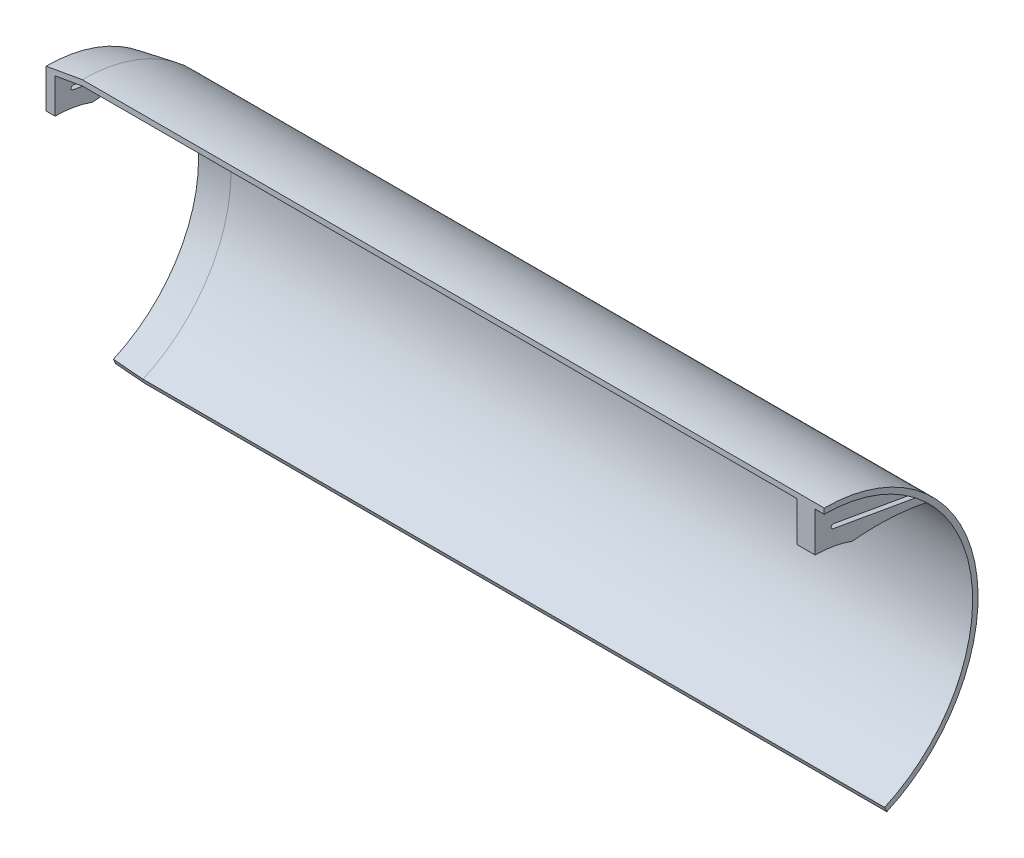
SolidWorks part; units mm, degrees
ref_plane "Front Plane" through (0, 0, 0) normal (0, 0, 1) x (1, 0, 0)
ref_plane "Top Plane" through (0, 0, 0) normal (0, 1, 0) x (1, 0, 0)
ref_plane "Right Plane" through (0, 0, 0) normal (1, 0, 0) x (0, 0, -1)
curve "Curve1"
  spline degree 3 poles (0, 0, 0) (-0.0123, 3.8916, 0) (-0.0274, 8.685, 0) (0.3616, 14.0857, 0) (0.5761, 16.0905, 0) (0.7825, 17.6048, 0) (0.9862, 18.8543, 0) (1.1887, 19.9315, 0) (1.3904, 20.8857, 0) (1.5917, 21.7465, 0) (1.7927, 22.5337, 0) (1.9935, 23.2611, 0) (2.1942, 23.9386, 0) (2.3947, 24.5739, 0) (2.5952, 25.1728, 0) (2.7956, 25.7401, 0) (2.9959, 26.2796, 0) (3.1962, 26.7943, 0) (3.3965, 27.2868, 0) (3.5967, 27.7594, 0) (3.7969, 28.2139, 0) (3.9971, 28.6519, 0) (4.1973, 29.0748, 0) (4.3974, 29.4838, 0) (4.5976, 29.8799, 0) (4.7977, 30.2641, 0) (4.9978, 30.6373, 0) (5.1979, 31.0001, 0) (5.398, 31.3533, 0) (5.5981, 31.6974, 0) (5.7982, 32.033, 0) (5.9983, 32.3606, 0) (6.1984, 32.6807, 0) (6.3985, 32.9935, 0) (6.5985, 33.2996, 0) (6.7986, 33.5993, 0) (6.9986, 33.8929, 0) (7.1987, 34.1806, 0) (7.3987, 34.4628, 0) (7.5988, 34.7397, 0) (7.7988, 35.0115, 0) (7.9989, 35.2785, 0) (8.1989, 35.5408, 0) (8.399, 35.7988, 0) (8.599, 36.0524, 0) (8.799, 36.3019, 0) (8.9991, 36.5476, 0) (9.1991, 36.7894, 0) (9.3991, 37.0275, 0) (9.5992, 37.2622, 0) (9.7992, 37.4934, 0) (9.9992, 37.7214, 0) (10.1992, 37.9461, 0) (10.3993, 38.1679, 0) (10.5993, 38.3866, 0) (10.7993, 38.6025, 0) (10.9993, 38.8156, 0) (11.1993, 39.026, 0) (11.3994, 39.2338, 0) (11.5994, 39.4391, 0) (11.7994, 39.6419, 0) (11.9994, 39.8422, 0) (12.1994, 40.0403, 0) (12.3995, 40.2361, 0) (12.5995, 40.4297, 0) (12.7995, 40.6212, 0) (12.9995, 40.8106, 0) (13.1995, 40.998, 0) (13.3995, 41.1834, 0) (13.5995, 41.3668, 0) (13.7995, 41.5484, 0) (13.9996, 41.7281, 0) (14.1996, 41.9061, 0) (14.3996, 42.0823, 0) (14.5996, 42.2568, 0) (14.7996, 42.4296, 0) (14.9996, 42.6008, 0) (15.1996, 42.7705, 0) (15.3996, 42.9385, 0) (15.5996, 43.1051, 0) (15.7996, 43.2701, 0) (15.9997, 43.4337, 0) (16.1997, 43.5959, 0) (16.3997, 43.7567, 0) (16.5997, 43.9161, 0) (16.7997, 44.0742, 0) (16.9997, 44.2309, 0) (17.1997, 44.3864, 0) (17.3997, 44.5406, 0) (17.5997, 44.6936, 0) (17.7997, 44.8453, 0) (17.9997, 44.9959, 0) (18.1997, 45.1453, 0) (18.3997, 45.2936, 0) (18.5997, 45.4407, 0) (18.7997, 45.5868, 0) (18.9997, 45.7317, 0) (19.1998, 45.8756, 0) (19.3998, 46.0185, 0) (19.5998, 46.1603, 0) (19.7998, 46.3011, 0) (19.9998, 46.4409, 0) (20.1998, 46.5797, 0) (20.3998, 46.7176, 0) (20.5998, 46.8546, 0) (20.7998, 46.9906, 0) (20.9998, 47.1257, 0) (21.1998, 47.2599, 0) (21.3998, 47.3932, 0) (21.5998, 47.5256, 0) (21.7998, 47.6572, 0) (21.9998, 47.788, 0) (22.1998, 47.9179, 0) (22.3998, 48.047, 0) (22.5998, 48.1753, 0) (22.7998, 48.3028, 0) (22.9998, 48.4295, 0) (23.1998, 48.5555, 0) (23.3998, 48.6807, 0) (23.5998, 48.8051, 0) (23.7998, 48.9288, 0) (23.9998, 49.0518, 0) (24.1998, 49.1741, 0) (24.3998, 49.2957, 0) (24.5998, 49.4165, 0) (24.7999, 49.5367, 0) (24.9999, 49.6562, 0) (25.1999, 49.7751, 0) (25.3999, 49.8933, 0) (25.5999, 50.0108, 0) (25.7999, 50.1277, 0) (25.9999, 50.2439, 0) (26.1999, 50.3596, 0) (26.3999, 50.4746, 0) (26.5999, 50.589, 0) (26.7999, 50.7028, 0) (26.9999, 50.8161, 0) (27.1999, 50.9287, 0) (27.3999, 51.0407, 0) (27.5999, 51.1522, 0) (27.7999, 51.2631, 0) (27.9999, 51.3735, 0) (28.1999, 51.4833, 0) (28.3999, 51.5926, 0) (28.5999, 51.7013, 0) (28.7999, 51.8095, 0) (28.9999, 51.9172, 0) (29.1999, 52.0243, 0) (29.3999, 52.131, 0) (29.5999, 52.2371, 0) (29.7999, 52.3428, 0) (29.9999, 52.4479, 0) (30.1999, 52.5526, 0) (30.3999, 52.6567, 0) (30.5999, 52.7604, 0) (30.7999, 52.8636, 0) (30.9999, 52.9664, 0) (31.1999, 53.0687, 0) (31.3999, 53.1705, 0) (31.5999, 53.2719, 0) (31.7999, 53.3728, 0) (31.9999, 53.4733, 0) (32.1999, 53.5733, 0) (32.3999, 53.6729, 0) (32.5999, 53.7721, 0) (32.7999, 53.8709, 0) (32.9999, 53.9692, 0) (33.1999, 54.0671, 0) (33.3999, 54.1646, 0) (33.5999, 54.2617, 0) (33.7999, 54.3584, 0) (33.9999, 54.4547, 0) (34.1999, 54.5506, 0) (34.3999, 54.6461, 0) (34.5999, 54.7412, 0) (34.7999, 54.836, 0) (34.9999, 54.9303, 0) (35.1999, 55.0243, 0) (35.3999, 55.1179, 0) (35.5999, 55.2111, 0) (35.7999, 55.304, 0) (35.9999, 55.3965, 0) (36.1999, 55.4887, 0) (36.3999, 55.5805, 0) (36.5999, 55.6719, 0) (36.7999, 55.763, 0) (36.9999, 55.8537, 0) (37.1999, 55.9441, 0) (37.3999, 56.0342, 0) (37.5999, 56.1239, 0) (37.7999, 56.2133, 0) (37.9999, 56.3024, 0) (38.1999, 56.3911, 0) (38.3999, 56.4795, 0) (38.5999, 56.5676, 0) (38.7999, 56.6554, 0) (38.9999, 56.7428, 0) (39.1999, 56.83, 0) (39.3999, 56.9168, 0) (39.5999, 57.0033, 0) (39.7999, 57.0896, 0) (39.9999, 57.1755, 0) (40.1999, 57.2611, 0) (40.3999, 57.3464, 0) (40.5999, 57.4314, 0) (40.7999, 57.5161, 0) (40.9999, 57.6006, 0) (41.1999, 57.6847, 0) (41.3999, 57.7686, 0) (41.6, 57.8522, 0) (41.8, 57.9355, 0) (42, 58.0185, 0) (42.2, 58.1012, 0) (42.4, 58.1837, 0) (42.6, 58.2659, 0) (42.8, 58.3479, 0) (43, 58.4295, 0) (43.2, 58.5109, 0) (43.4, 58.592, 0) (43.6, 58.6729, 0) (43.8, 58.7535, 0) (44, 58.8339, 0) (44.2, 58.914, 0) (44.4, 58.9938, 0) (44.6, 59.0734, 0) (44.8, 59.1528, 0) (45, 59.2319, 0) (45.2, 59.3107, 0) (45.4, 59.3893, 0) (45.6, 59.4677, 0) (45.8, 59.5458, 0) (46, 59.6237, 0) (46.2, 59.7014, 0) (46.4, 59.7788, 0) (46.6, 59.856, 0) (46.8, 59.9329, 0) (47, 60.0096, 0) (47.2, 60.0861, 0) (47.4, 60.1624, 0) (47.6, 60.2385, 0) (47.8, 60.3143, 0) (48, 60.3899, 0) (48.2, 60.4652, 0) (48.4, 60.5404, 0) (48.6, 60.6153, 0) (48.8, 60.6901, 0) (49, 60.7646, 0) (49.2, 60.8389, 0) (49.4, 60.913, 0) (49.6, 60.9869, 0) (49.8, 61.0605, 0) (50, 61.134, 0) (50.2, 61.2072, 0) (50.4, 61.2803, 0) (50.6, 61.3531, 0) (50.8, 61.4258, 0) (51, 61.4982, 0) (51.2, 61.5705, 0) (51.4, 61.6426, 0) (51.6, 61.7144, 0) (51.8, 61.7861, 0) (52, 61.8575, 0) (52.2, 61.9288, 0) (52.4, 61.9999, 0) (52.6, 62.0708, 0) (52.8, 62.1415, 0) (53, 62.212, 0) (53.2, 62.2824, 0) (53.4, 62.3525, 0) (53.6, 62.4225, 0) (53.8, 62.4923, 0) (54, 62.5619, 0) (54.2, 62.6313, 0) (54.4, 62.7006, 0) (54.6, 62.7696, 0) (54.8, 62.8385, 0) (55, 62.9072, 0) (55.2, 62.9758, 0) (55.4, 63.0441, 0) (55.6, 63.1123, 0) (55.8, 63.1803, 0) (56, 63.2482, 0) (56.2, 63.3159, 0) (56.4, 63.3834, 0) (56.6, 63.4507, 0) (56.8, 63.5179, 0) (57, 63.5849, 0) (57.2, 63.6518, 0) (57.4, 63.7185, 0) (57.6, 63.785, 0) (57.8, 63.8513, 0) (58, 63.9175, 0) (58.2, 63.9836, 0) (58.4, 64.0495, 0) (58.6, 64.1152, 0) (58.8, 64.1808, 0) (59, 64.2462, 0) (59.2, 64.3114, 0) (59.4, 64.3765, 0) (59.6, 64.4415, 0) (59.8, 64.5063, 0) (60, 64.5709, 0) (60.2, 64.6354, 0) (60.4, 64.6998, 0) (60.6, 64.764, 0) (60.8, 64.828, 0) (61, 64.8919, 0) (61.2, 64.9557, 0) (61.4, 65.0193, 0) (61.6, 65.0827, 0) (61.8, 65.1461, 0) (62, 65.2092, 0) (62.2, 65.2723, 0) (62.4, 65.3352, 0) (62.6, 65.3979, 0) (62.8, 65.4605, 0) (63, 65.523, 0) (63.2, 65.5853, 0) (63.4, 65.6475, 0) (63.6, 65.7096, 0) (63.8, 65.7715, 0) (64, 65.8333, 0) (64.2, 65.895, 0) (64.4, 65.9565, 0) (64.6, 66.0179, 0) (64.8, 66.0791, 0) (65, 66.1402, 0) (65.2, 66.2012, 0) (65.4, 66.2621, 0) (65.6, 66.3228, 0) (65.8, 66.3834, 0) (66, 66.4439, 0) (66.2, 66.5042, 0) (66.4, 66.5644, 0) (66.6, 66.6245, 0) (66.8, 66.6845, 0) (67, 66.7443, 0) (67.2, 66.804, 0) (67.4, 66.8636, 0) (67.6, 66.923, 0) (67.8, 66.9824, 0) (68, 67.0416, 0) (68.2, 67.1007, 0) (68.4, 67.1597, 0) (68.6, 67.2185, 0) (68.8, 67.2772, 0) (69, 67.3359, 0) (69.2, 67.3943, 0) (69.4, 67.4527, 0) (69.6, 67.511, 0) (69.8, 67.5691, 0) (70, 67.6271, 0) (70.2, 67.6851, 0) (70.4, 67.7428, 0) (70.6, 67.8005, 0) (70.8, 67.8581, 0) (71, 67.9155, 0) (71.2, 67.9729, 0) (71.4, 68.0301, 0) (71.6, 68.0872, 0) (71.8, 68.1442, 0) (72, 68.2011, 0) (72.2, 68.2579, 0) (72.4, 68.3145, 0) (72.6, 68.3711, 0) (72.8, 68.4276, 0) (73, 68.4839, 0) (73.2, 68.5401, 0) (73.4, 68.5963, 0) (73.6, 68.6523, 0) (73.8, 68.7082, 0) (74, 68.764, 0) (74.2, 68.8197, 0) (74.4, 68.8753, 0) (74.6, 68.9308, 0) (74.8, 68.9862, 0) (75, 69.0415, 0) (75.2, 69.0966, 0) (75.4, 69.1517, 0) (75.6, 69.2067, 0) (75.8, 69.2616, 0) (76, 69.3164, 0) (76.2, 69.371, 0) (76.4, 69.4256, 0) (76.6, 69.4801, 0) (76.8, 69.5344, 0) (77, 69.5887, 0) (77.2, 69.6429, 0) (77.4, 69.697, 0) (77.6, 69.751, 0) (77.8, 69.8048, 0) (78, 69.8586, 0) (78.2, 69.9123, 0) (78.4, 69.9659, 0) (78.6, 70.0194, 0) (78.8, 70.0728, 0) (79, 70.1261, 0) (79.2, 70.1793, 0) (79.4, 70.2324, 0) (79.6, 70.2855, 0) (79.8, 70.3384, 0) (80, 70.3912, 0) (80.2, 70.444, 0) (80.4, 70.4966, 0) (80.6, 70.5492, 0) (80.8, 70.6017, 0) (81, 70.6541, 0) (81.2, 70.7064, 0) (81.4, 70.7586, 0) (81.6, 70.8107, 0) (81.8, 70.8627, 0) (82, 70.9146, 0) (82.2, 70.9665, 0) (82.4, 71.0182, 0) (82.6, 71.0699, 0) (82.8, 71.1215, 0) (83, 71.173, 0) (83.2, 71.2244, 0) (83.4, 71.2757, 0) (83.6, 71.3269, 0) (83.8, 71.3781, 0) (84, 71.4291, 0) (84.2, 71.4801, 0) (84.4, 71.531, 0) (84.6, 71.5818, 0) (84.8, 71.6325, 0) (85, 71.6832, 0) (85.2, 71.7337, 0) (85.4, 71.7842, 0) (85.6, 71.8346, 0) (85.8, 71.8849, 0) (86, 71.9351, 0) (86.2, 71.9853, 0) (86.4, 72.0354, 0) (86.6, 72.0853, 0) (86.8, 72.1352, 0) (87, 72.1851, 0) (87.2, 72.2348, 0) (87.4, 72.2845, 0) (87.6, 72.3341, 0) (87.8, 72.3836, 0) (88, 72.433, 0) (88.2, 72.4823, 0) (88.4, 72.5316, 0) (88.6, 72.5808, 0) (88.8, 72.6299, 0) (89, 72.6789, 0) (89.2, 72.7279, 0) (89.4, 72.7768, 0) (89.6, 72.8256, 0) (89.8, 72.8743, 0) (90, 72.923, 0) (90.2, 72.9716, 0) (90.4, 73.0201, 0) (90.6, 73.0685, 0) (90.8, 73.1168, 0) (91, 73.1651, 0) (91.2, 73.2133, 0) (91.4, 73.2614, 0) (91.6, 73.3095, 0) (91.8, 73.3575, 0) (92, 73.4054, 0) (92.2, 73.4532, 0) (92.4, 73.501, 0) (92.6, 73.5487, 0) (92.8, 73.5963, 0) (93, 73.6439, 0) (93.2, 73.6913, 0) (93.4, 73.7387, 0) (93.6, 73.7861, 0) (93.8, 73.8333, 0) (94, 73.8805, 0) (94.2, 73.9276, 0) (94.4, 73.9747, 0) (94.6, 74.0217, 0) (94.8, 74.0686, 0) (95, 74.1154, 0) (95.2, 74.1622, 0) (95.4, 74.2089, 0) (95.6, 74.2556, 0) (95.8, 74.3021, 0) (96, 74.3486, 0) (96.2, 74.3951, 0) (96.4, 74.4414, 0) (96.6, 74.4877, 0) (96.8, 74.534, 0) (97, 74.5801, 0) (97.2, 74.6262, 0) (97.4, 74.6723, 0) (97.6, 74.7182, 0) (97.8, 74.7641, 0) (98, 74.81, 0) (98.2, 74.8557, 0) (98.4, 74.9014, 0) (98.6, 74.9471, 0) (98.8, 74.9926, 0) (99, 75.0382, 0) (99.2, 75.0836, 0) (99.4, 75.129, 0) (99.6, 75.1743, 0) (99.8, 75.2196, 0) (100, 75.2647, 0) (100.2, 75.3099, 0) (100.4, 75.3549, 0) (100.6, 75.3999, 0) (100.8, 75.4449, 0) (101, 75.4898, 0) (101.2, 75.5346, 0) (101.4, 75.5793, 0) (101.6, 75.624, 0) (101.8, 75.6686, 0) (102, 75.7132, 0) (102.2, 75.7577, 0) (102.4, 75.8022, 0) (102.6, 75.8465, 0) (102.8, 75.8909, 0) (103, 75.9351, 0) (103.2, 75.9793, 0) (103.4, 76.0235, 0) (103.6, 76.0676, 0) (103.8, 76.1116, 0) (104, 76.1556, 0) (104.2, 76.1995, 0) (104.4, 76.2433, 0) (104.6, 76.2871, 0) (104.8, 76.3308, 0) (105, 76.3745, 0) (105.2, 76.4181, 0) (105.4, 76.4617, 0) (105.6, 76.5052, 0) (105.8, 76.5486, 0) (106, 76.592, 0) (106.2, 76.6353, 0) (106.4, 76.6786, 0) (106.6, 76.7218, 0) (106.8, 76.7649, 0) (107, 76.808, 0) (107.2, 76.8511, 0) (107.4, 76.8941, 0) (107.6, 76.937, 0) (107.8, 76.9799, 0) (108, 77.0227, 0) (108.2, 77.0655, 0) (108.4, 77.1082, 0) (108.6, 77.1508, 0) (108.8, 77.1934, 0) (109, 77.236, 0) (109.2, 77.2784, 0) (109.4, 77.3209, 0) (109.6, 77.3633, 0) (109.8, 77.4056, 0) (110, 77.4479, 0) (110.2, 77.4901, 0) (110.4, 77.5322, 0) (110.6, 77.5743, 0) (110.8, 77.6164, 0) (111, 77.6584, 0) (111.2, 77.7004, 0) (111.4, 77.7423, 0) (111.6, 77.7841, 0) (111.8, 77.8259, 0) (112, 77.8676, 0) (112.2, 77.9093, 0) (112.4, 77.951, 0) (112.6, 77.9925, 0) (112.8, 78.0341, 0) (113, 78.0756, 0) (113.2, 78.117, 0) (113.4, 78.1584, 0) (113.6, 78.1997, 0) (113.8, 78.241, 0) (114, 78.2822, 0) (114.2, 78.3234, 0) (114.4, 78.3645, 0) (114.6, 78.4056, 0) (114.8, 78.4466, 0) (115, 78.4876, 0) (115.2, 78.5285, 0) (115.4, 78.5694, 0) (115.6, 78.6102, 0) (115.8, 78.651, 0) (116, 78.6917, 0) (116.2, 78.7324, 0) (116.4, 78.773, 0) (116.6, 78.8136, 0) (116.8, 78.8541, 0) (117, 78.8946, 0) (117.2, 78.935, 0) (117.4, 78.9754, 0) (117.6, 79.0158, 0) (117.8, 79.0561, 0) (118, 79.0963, 0) (118.2, 79.1365, 0) (118.4, 79.1766, 0) (118.6, 79.2167, 0) (118.8, 79.2568, 0) (119, 79.2968, 0) (119.2, 79.3368, 0) (119.4, 79.3767, 0) (119.6, 79.4165, 0) (119.8, 79.4564, 0) (120, 79.4961, 0) (120.2, 79.5358, 0) (120.4, 79.5755, 0) (120.6, 79.6152, 0) (120.8, 79.6547, 0) (121, 79.6943, 0) (121.2, 79.7338, 0) (121.4, 79.7732, 0) (121.6, 79.8126, 0) (121.8, 79.852, 0) (122, 79.8913, 0) (122.2, 79.9306, 0) (122.4, 79.9698, 0) (122.6, 80.009, 0) (122.8, 80.0481, 0) (123, 80.0872, 0) (123.2, 80.1262, 0) (123.4, 80.1652, 0) (123.6, 80.2042, 0) (123.8, 80.2431, 0) (124, 80.282, 0) (124.2, 80.3208, 0) (124.4, 80.3596, 0) (124.6, 80.3983, 0) (124.8, 80.437, 0) (125, 80.4757, 0) (125.2, 80.5143, 0) (125.4, 80.5528, 0) (125.6, 80.5914, 0) (125.8, 80.6298, 0) (126, 80.6683, 0) (126.2, 80.7067, 0) (126.4, 80.745, 0) (126.6, 80.7833, 0) (126.8, 80.8216, 0) (127, 80.8598, 0) (127.2, 80.898, 0) (127.4, 80.9361, 0) (127.6, 80.9742, 0) (127.8, 81.0123, 0) (128, 81.0503, 0) (128.2, 81.0883, 0) (128.4, 81.1262, 0) (128.6, 81.1641, 0) (128.8, 81.2019, 0) (129, 81.2397, 0) (129.2, 81.2775, 0) (129.4, 81.3152, 0) (129.6, 81.3529, 0) (129.8, 81.3906, 0) (130, 81.4282, 0) (130.2, 81.4657, 0) (130.4, 81.5032, 0) (130.6, 81.5407, 0) (130.8, 81.5782, 0) (131, 81.6156, 0) (131.2, 81.6529, 0) (131.4, 81.6902, 0) (131.6, 81.7275, 0) (131.8, 81.7648, 0) (132, 81.802, 0) (132.2, 81.8391, 0) (132.4, 81.8763, 0) (132.6, 81.9133, 0) (132.8, 81.9504, 0) (133, 81.9874, 0) (133.2, 82.0244, 0) (133.4, 82.0613, 0) (133.6, 82.0982, 0) (133.8, 82.135, 0) (134, 82.1718, 0) (134.2, 82.2086, 0) (134.4, 82.2454, 0) (134.6, 82.282, 0) (134.8, 82.3187, 0) (135, 82.3553, 0) (135.2, 82.3919, 0) (135.4, 82.4285, 0) (135.6, 82.465, 0) (135.8, 82.5014, 0) (136, 82.5379, 0) (136.2, 82.5743, 0) (136.4, 82.6106, 0) (136.6, 82.6469, 0) (136.8, 82.6832, 0) (137, 82.7195, 0) (137.2, 82.7557, 0) (137.4, 82.7919, 0) (137.6, 82.828, 0) (137.8, 82.8641, 0) (138, 82.9001, 0) (138.2, 82.9362, 0) (138.4, 82.9722, 0) (138.6, 83.0081, 0) (138.8, 83.044, 0) (139, 83.0799, 0) (139.2, 83.1158, 0) (139.4, 83.1516, 0) (139.6, 83.1873, 0) (139.8, 83.2231, 0) (140, 83.2588, 0) (140.2, 83.2944, 0) (140.4, 83.3301, 0) (140.6, 83.3657, 0) (140.8, 83.4012, 0) (141, 83.4367, 0) (141.2, 83.4722, 0) (141.4, 83.5077, 0) (141.6, 83.5431, 0) (141.8, 83.5785, 0) (142, 83.6138, 0) (142.2, 83.6491, 0) (142.4, 83.6844, 0) (142.6, 83.7197, 0) (142.8, 83.7549, 0) (143, 83.79, 0) (143.2, 83.8252, 0) (143.4, 83.8603, 0) (143.6, 83.8954, 0) (143.8, 83.9304, 0) (144, 83.9654, 0) (144.2, 84.0004, 0) (144.4, 84.0353, 0) (144.6, 84.0702, 0) (144.8, 84.1051, 0) (145, 84.1399, 0) (145.2, 84.1747, 0) (145.4, 84.2095, 0) (145.6, 84.2442, 0) (145.8, 84.2789, 0) (146, 84.3136, 0) (146.2, 84.3482, 0) (146.4, 84.3828, 0) (146.6, 84.4174, 0) (146.8, 84.4519, 0) (147, 84.4864, 0) (147.2, 84.5209, 0) (147.4, 84.5553, 0) (147.6, 84.5897, 0) (147.8, 84.6241, 0) (148, 84.6584, 0) (148.2, 84.6927, 0) (148.4, 84.727, 0) (148.6, 84.7612, 0) (148.8, 84.7954, 0) (149, 84.8296, 0) (149.2, 84.8638, 0) (149.4, 84.8979, 0) (149.6, 84.9319, 0) (149.8, 84.966, 0) (149.9333, 84.9887, 0) (150, 85, 0) knots 0 0 0 0 0.061462 0.075706 0.085548 0.093322 0.099856 0.105554 0.110643 0.115268 0.119525 0.123482 0.127192 0.130691 0.13401 0.137173 0.140199 0.143104 0.145901 0.148602 0.151215 0.15375 0.156213 0.158609 0.160946 0.163227 0.165456 0.167638 0.169775 0.171871 0.173928 0.17595 0.177937 0.179893 0.181819 0.183716 0.185587 0.187433 0.189255 0.191054 0.192831 0.194589 0.196326 0.198045 0.199747 0.201431 0.2031 0.204753 0.206391 0.208015 0.209626 0.211223 0.212808 0.214381 0.215942 0.217493 0.219032 0.220561 0.22208 0.22359 0.225091 0.226582 0.228065 0.229539 0.231006 0.232464 0.233915 0.235359 0.236795 0.238225 0.239648 0.241065 0.242475 0.243879 0.245277 0.24667 0.248057 0.249438 0.250814 0.252185 0.253551 0.254913 0.256269 0.257621 0.258968 0.260311 0.26165 0.262984 0.264315 0.265641 0.266964 0.268282 0.269598 0.270909 0.272217 0.273522 0.274823 0.276121 0.277416 0.278707 0.279996 0.281281 0.282564 0.283843 0.28512 0.286394 0.287666 0.288935 0.290201 0.291465 0.292726 0.293985 0.295241 0.296495 0.297747 0.298996 0.300243 0.301489 0.302732 0.303972 0.305211 0.306448 0.307683 0.308916 0.310147 0.311376 0.312604 0.313829 0.315053 0.316275 0.317495 0.318714 0.319931 0.321147 0.32236 0.323573 0.324783 0.325993 0.3272 0.328406 0.329611 0.330815 0.332017 0.333217 0.334416 0.335614 0.336811 0.338006 0.3392 0.340393 0.341584 0.342775 0.343964 0.345152 0.346339 0.347524 0.348709 0.349892 0.351074 0.352256 0.353436 0.354615 0.355793 0.35697 0.358146 0.359321 0.360495 0.361668 0.36284 0.364011 0.365182 0.366351 0.36752 0.368687 0.369854 0.37102 0.372185 0.373349 0.374512 0.375674 0.376836 0.377997 0.379157 0.380316 0.381475 0.382632 0.383789 0.384946 0.386101 0.387256 0.38841 0.389563 0.390716 0.391868 0.393019 0.39417 0.39532 0.396469 0.397618 0.398766 0.399913 0.40106 0.402206 0.403351 0.404496 0.40564 0.406784 0.407927 0.409069 0.410211 0.411353 0.412493 0.413633 0.414773 0.415912 0.417051 0.418189 0.419326 0.420463 0.4216 0.422736 0.423871 0.425006 0.426141 0.427275 0.428408 0.429541 0.430674 0.431806 0.432937 0.434068 0.435199 0.436329 0.437459 0.438588 0.439717 0.440846 0.441974 0.443101 0.444229 0.445355 0.446482 0.447608 0.448733 0.449858 0.450983 0.452107 0.453231 0.454355 0.455478 0.456601 0.457723 0.458845 0.459967 0.461088 0.462209 0.46333 0.46445 0.46557 0.46669 0.467809 0.468928 0.470046 0.471164 0.472282 0.4734 0.474517 0.475634 0.47675 0.477866 0.478982 0.480098 0.481213 0.482328 0.483443 0.484557 0.485671 0.486785 0.487898 0.489011 0.490124 0.491237 0.492349 0.493461 0.494573 0.495684 0.496796 0.497906 0.499017 0.500127 0.501237 0.502347 0.503457 0.504566 0.505675 0.506784 0.507892 0.509001 0.510109 0.511216 0.512324 0.513431 0.514538 0.515645 0.516752 0.517858 0.518964 0.52007 0.521175 0.522281 0.523386 0.524491 0.525595 0.5267 0.527804 0.528908 0.530012 0.531116 0.532219 0.533322 0.534425 0.535528 0.53663 0.537733 0.538835 0.539937 0.541038 0.54214 0.543241 0.544342 0.545443 0.546544 0.547644 0.548745 0.549845 0.550945 0.552044 0.553144 0.554243 0.555342 0.556441 0.55754 0.558639 0.559737 0.560836 0.561934 0.563032 0.564129 0.565227 0.566324 0.567421 0.568518 0.569615 0.570712 0.571809 0.572905 0.574001 0.575097 0.576193 0.577289 0.578384 0.57948 0.580575 0.58167 0.582765 0.58386 0.584954 0.586049 0.587143 0.588237 0.589331 0.590425 0.591519 0.592612 0.593706 0.594799 0.595892 0.596985 0.598078 0.59917 0.600263 0.601355 0.602448 0.60354 0.604632 0.605724 0.606815 0.607907 0.608998 0.61009 0.611181 0.612272 0.613363 0.614453 0.615544 0.616635 0.617725 0.618815 0.619905 0.620995 0.622085 0.623175 0.624265 0.625354 0.626443 0.627533 0.628622 0.629711 0.6308 0.631888 0.632977 0.634066 0.635154 0.636242 0.637331 0.638419 0.639507 0.640594 0.641682 0.64277 0.643857 0.644945 0.646032 0.647119 0.648206 0.649293 0.65038 0.651467 0.652553 0.65364 0.654726 0.655813 0.656899 0.657985 0.659071 0.660157 0.661243 0.662328 0.663414 0.664499 0.665585 0.66667 0.667755 0.66884 0.669925 0.67101 0.672095 0.67318 0.674264 0.675349 0.676433 0.677518 0.678602 0.679686 0.68077 0.681854 0.682938 0.684022 0.685105 0.686189 0.687272 0.688356 0.689439 0.690522 0.691605 0.692688 0.693771 0.694854 0.695937 0.69702 0.698102 0.699185 0.700267 0.70135 0.702432 0.703514 0.704596 0.705678 0.70676 0.707842 0.708924 0.710006 0.711087 0.712169 0.71325 0.714332 0.715413 0.716494 0.717575 0.718656 0.719737 0.720818 0.721899 0.72298 0.724061 0.725141 0.726222 0.727302 0.728382 0.729463 0.730543 0.731623 0.732703 0.733783 0.734863 0.735943 0.737023 0.738103 0.739182 0.740262 0.741341 0.742421 0.7435 0.744579 0.745659 0.746738 0.747817 0.748896 0.749975 0.751054 0.752133 0.753211 0.75429 0.755369 0.756447 0.757526 0.758604 0.759682 0.760761 0.761839 0.762917 0.763995 0.765073 0.766151 0.767229 0.768307 0.769385 0.770462 0.77154 0.772618 0.773695 0.774773 0.77585 0.776927 0.778005 0.779082 0.780159 0.781236 0.782313 0.78339 0.784467 0.785544 0.786621 0.787698 0.788774 0.789851 0.790928 0.792004 0.793081 0.794157 0.795233 0.79631 0.797386 0.798462 0.799538 0.800614 0.80169 0.802766 0.803842 0.804918 0.805994 0.80707 0.808145 0.809221 0.810296 0.811372 0.812447 0.813523 0.814598 0.815674 0.816749 0.817824 0.818899 0.819974 0.821049 0.822124 0.823199 0.824274 0.825349 0.826424 0.827499 0.828573 0.829648 0.830723 0.831797 0.832872 0.833946 0.835021 0.836095 0.837169 0.838244 0.839318 0.840392 0.841466 0.84254 0.843614 0.844688 0.845762 0.846836 0.84791 0.848984 0.850058 0.851131 0.852205 0.853279 0.854352 0.855426 0.856499 0.857573 0.858646 0.859719 0.860793 0.861866 0.862939 0.864012 0.865085 0.866159 0.867232 0.868305 0.869378 0.87045 0.871523 0.872596 0.873669 0.874742 0.875814 0.876887 0.87796 0.879032 0.880105 0.881177 0.88225 0.883322 0.884395 0.885467 0.886539 0.887611 0.888684 0.889756 0.890828 0.8919 0.892972 0.894044 0.895116 0.896188 0.89726 0.898332 0.899404 0.900475 0.901547 0.902619 0.90369 0.904762 0.905834 0.906905 0.907977 0.909048 0.91012 0.911191 0.912262 0.913334 0.914405 0.915476 0.916548 0.917619 0.91869 0.919761 0.920832 0.921903 0.922974 0.924045 0.925116 0.926187 0.927258 0.928329 0.929399 0.93047 0.931541 0.932612 0.933682 0.934753 0.935823 0.936894 0.937965 0.939035 0.940105 0.941176 0.942246 0.943317 0.944387 0.945457 0.946527 0.947598 0.948668 0.949738 0.950808 0.951878 0.952948 0.954018 0.955088 0.956158 0.957228 0.958298 0.959368 0.960438 0.961508 0.962577 0.963647 0.964717 0.965786 0.966856 0.967926 0.968995 0.970065 0.971134 0.972204 0.973273 0.974343 0.975412 0.976481 0.977551 0.97862 0.979689 0.980759 0.981828 0.982897 0.983966 0.985035 0.986104 0.987173 0.988242 0.989311 0.99038 0.991449 0.992518 0.993587 0.994656 0.995725 0.996794 0.997863 0.998931 1 1 1 1
sketch "Sketch1" plane through (0, 0, 0) normal (0, 0, 1) x (1, 0, 0)
  line L0 (150, 85) -> (560, 85)
  line L1 (150.2533, 82) -> (560, 82)
  line L2 (560, 85) -> (560, 82)
  line L3 (0, 0) -> (3, 0)
  line L4 (3, 0.0095) -> (3, 0)
  line L5 (3, 0) -> (560, 0) construction
  line L6 (560, 0) -> (560, 82) construction
  line L7 (540, 75) -> (135, 75) construction
  line L8 (135, 75) -> (135, 0) construction
  line L9 (130, 78.3755) -> (135, 78.3755)
  line L12 (135, 79.3054) -> (135, 60)
  line L13 (135, 60) -> (130, 60)
  line L14 (130, 60) -> (130, 81.4281)
  line L15 (555, 60) -> (555, 82)
  line L16 (545, 82) -> (545, 60)
  line L17 (545, 60) -> (555, 60)
  spline S0 degree 3 poles (-1988.6566, -159.7184) (98.3599, -158.1291) (-5.7084, -70.1856) (0.3616, 14.0857) (0.5761, 16.0905) (0.7825, 17.6048) (0.9862, 18.8543) (1.1887, 19.9315) (1.3904, 20.8857) (1.5917, 21.7465) (1.7927, 22.5337) (1.9935, 23.2611) (2.2538, 24.14) (2.5806, 25.1462) (2.9836, 26.2595) (3.3859, 27.2713) (3.7877, 28.2016) (4.1891, 29.0648) (4.5903, 29.8717) (5.0533, 30.7478) (5.5832, 31.6835) (6.1854, 32.6697) (6.7872, 33.5906) (7.4515, 34.5461) (8.1828, 35.531) (8.9851, 36.54) (9.8503, 37.5625) (10.7826, 38.5957) (11.785, 39.6369) (12.851, 40.6804) (13.984, 41.7246) (15.1862, 42.7682) (16.388, 43.7553) (17.6544, 44.7435) (18.9876, 45.7315) (20.3892, 46.7179) (21.7905, 47.6579) (23.2571, 48.5984) (24.7904, 49.5382) (26.3916, 50.4762) (28.0583, 51.4122) (29.7917, 52.3451) (31.5927, 53.2742) (33.4594, 54.1996) (35.3929, 55.1207) (37.4597, 56.0672) (39.5933, 57.0066) (41.8602, 57.9666) (44.1937, 58.9175) (46.6606, 59.8853) (49.2604, 60.8677) (51.994, 61.8617) (54.861, 62.8656) (57.7946, 63.8556) (60.8615, 64.8536) (64.0615, 65.8584) (67.4615, 66.8882) (70.9951, 67.9202) (74.6621, 68.9539) (78.4621, 69.9886) (82.4622, 71.0404) (86.6623, 72.1071) (91.0624, 73.1864) (95.6625, 74.2764) (100.4626, 75.3753) (105.4628, 76.4816) (110.6629, 77.5938) (116.063, 78.7107) (121.6632, 79.8312) (127.5299, 80.9671) (133.6633, 82.1162) (140.0634, 83.2764) (145.1985, 84.1774) (148.3332, 84.7158) (149.3333, 84.8865) (149.6, 84.9319) (194.4783, 92.5723) (239.7917, 97.2513) (-50.3187, 2073.1568) knots -1.249314 -1.249314 -1.249314 -1.249314 0.061462 0.075706 0.085548 0.093322 0.099856 0.105554 0.110643 0.115268 0.119525 0.123482 0.127192 0.13401 0.140199 0.145901 0.151215 0.156213 0.160946 0.165456 0.171871 0.177937 0.183716 0.189255 0.196326 0.2031 0.209626 0.217493 0.225091 0.232464 0.241065 0.249438 0.257621 0.265641 0.274823 0.283843 0.292726 0.301489 0.311376 0.321147 0.330815 0.341584 0.352256 0.36284 0.374512 0.386101 0.398766 0.411353 0.425006 0.438588 0.453231 0.468928 0.484557 0.501237 0.517858 0.535528 0.554243 0.574001 0.593706 0.614453 0.636242 0.659071 0.682938 0.707842 0.733783 0.760761 0.788774 0.817824 0.84791 0.879032 0.912262 0.946527 0.981828 0.994656 0.996794 0.997863 0.998931 1.716252 1.716252 1.716252 1.716252 only from (0, 0) to (150, 85) construction
  spline S1 degree 3 poles (0, 0) (-0.0123, 3.8916) (-0.0274, 8.685) (0.3616, 14.0857) (0.5761, 16.0905) (0.7825, 17.6048) (0.9862, 18.8543) (1.1887, 19.9315) (1.3904, 20.8857) (1.5917, 21.7465) (1.7927, 22.5337) (1.9935, 23.2611) (2.2538, 24.14) (2.5806, 25.1462) (2.9836, 26.2595) (3.3859, 27.2713) (3.7877, 28.2016) (4.1891, 29.0648) (4.5903, 29.8717) (5.0533, 30.7478) (5.5832, 31.6835) (6.1854, 32.6697) (6.7872, 33.5906) (7.4515, 34.5461) (8.1828, 35.531) (8.9851, 36.54) (9.8503, 37.5625) (10.7826, 38.5957) (11.785, 39.6369) (12.851, 40.6804) (13.984, 41.7246) (15.1862, 42.7682) (16.388, 43.7553) (17.6544, 44.7435) (18.9876, 45.7315) (20.3892, 46.7179) (21.7905, 47.6579) (23.2571, 48.5984) (24.7904, 49.5382) (26.3916, 50.4762) (28.0583, 51.4122) (29.7917, 52.3451) (31.5927, 53.2742) (33.4594, 54.1996) (35.3929, 55.1207) (37.4597, 56.0672) (39.5933, 57.0066) (41.8602, 57.9666) (44.1937, 58.9175) (46.6606, 59.8853) (49.2604, 60.8677) (51.994, 61.8617) (54.861, 62.8656) (57.7946, 63.8556) (60.8615, 64.8536) (64.0615, 65.8584) (67.4615, 66.8882) (70.9951, 67.9202) (74.6621, 68.9539) (78.4621, 69.9886) (82.4622, 71.0404) (86.6623, 72.1071) (91.0624, 73.1864) (95.6625, 74.2764) (100.4626, 75.3753) (105.4628, 76.4816) (110.6629, 77.5938) (116.063, 78.7107) (121.6632, 79.8312) (127.5299, 80.9671) (133.6633, 82.1162) (140.0634, 83.2764) (145.1985, 84.1774) (148.3332, 84.7158) (149.4, 84.8979) (149.7333, 84.9547) (149.9333, 84.9887) (150, 85) knots 0 0 0 0 0.061462 0.075706 0.085548 0.093322 0.099856 0.105554 0.110643 0.115268 0.119525 0.123482 0.127192 0.13401 0.140199 0.145901 0.151215 0.156213 0.160946 0.165456 0.171871 0.177937 0.183716 0.189255 0.196326 0.2031 0.209626 0.217493 0.225091 0.232464 0.241065 0.249438 0.257621 0.265641 0.274823 0.283843 0.292726 0.301489 0.311376 0.321147 0.330815 0.341584 0.352256 0.36284 0.374512 0.386101 0.398766 0.411353 0.425006 0.438588 0.453231 0.468928 0.484557 0.501237 0.517858 0.535528 0.554243 0.574001 0.593706 0.614453 0.636242 0.659071 0.682938 0.707842 0.733783 0.760761 0.788774 0.817824 0.84791 0.879032 0.912262 0.946527 0.981828 0.994656 0.996794 0.998931 1 1 1 1
  spline S4 degree 1 poles (3, 0.0095) (150.2533, 82) knots 0 0 1 1 construction
  spline S5 degree 3 poles (3, 0.0095) (2.9938, 1.9694) (2.982, 5.9112) (3.1447, 11.6915) (3.6709, 17.3262) (4.8192, 22.7297) (6.752, 27.816) (10.434, 34.0689) (16.886, 40.7698) (26.3115, 47.2193) (36.5885, 52.5329) (47.3393, 57.0416) (62.0527, 62.2707) (80.8898, 67.7174) (103.8331, 73.1782) (119.8433, 76.4414) (128.9979, 78.1869) (130.8328, 78.5327) (132.4993, 78.8436) (134.1662, 79.1526) (140.0771, 80.2373) (145.5819, 81.205) (150.2533, 82) knots 0 0 0 0 0.031208 0.062417 0.093625 0.124833 0.156041 0.18725 0.249666 0.312083 0.374499 0.436916 0.499332 0.624165 0.748998 0.873831 0.883277 0.89671 0.903427 0.910144 0.923577 0.998664 0.998664 0.998664 0.998664
  dimension "D2" = 410
  dimension "D4" = 75
  dimension "D5" = 405
  dimension "D6" = 20
  dimension "D7" = 10
  dimension "D1" = 5
  dimension "D8" = 60
  dimension "D9" = 10
  dimension "D3" = 3
revolve "Revolve5" add sketch "Sketch1" angle 156 about L5 region at (344.8477, 83.4159, 0) region at (133.3296, 78.6861, 0) region at (132.5, 69.1877, 0) region at (550, 71, 0) reverse direction yes
ref_axis "Axis1" through (150, -77.6514, -34.5726) along (1, 0, 0)
ref_plane "Plane1" through (135, 0, 0) normal (1, 0, 0) x (0, 0, -1)
revolve "Revolve7" add sketch "Sketch1<9>" angle 50 about L5 region at (344.8477, 83.4159, 0) reverse direction yes
sketch "Sketch1<9>" plane through (0, 0, 0) normal (0, 0, 1) x (1, 0, 0) same geometry as "Sketch1"
sketch "Sketch4" plane through (135, 0, 0) normal (-1, 0, 0) x (0, 0, 1)
  line L0 (0, 0) -> (-28.1672, 77.3887) construction
  line L1 (0, -89.4583) -> (0, 89.4583) construction
  line L2 (0, 60) -> (0, 82.3553)
  line L6 (0, 0) -> (-10.4189, 59.0885) construction
  line L7 (-57.113, 59.3338) -> (-9.8003, 67.6764)
  line L8 (-53.9452, 62.2279) -> (-10.1997, 69.9414)
  arc A1 (0, 82.3553) -> (-33.4969, -75.2353) centre (0, 0) ccw
  arc A2 (0, 82.3553) -> (-53.9452, 62.2279) centre (0, 0) ccw
  arc A5 (0, 60) -> (-24.4042, -54.8127) centre (0, 0) ccw construction
  arc A8 (0, 60) -> (-20.5212, 56.3816) centre (0, 0) ccw
  arc A9 (-9.8003, 67.6764) -> (-10.1997, 69.9414) centre (-10, 68.8089) ccw
  arc A10 (-20.5212, 56.3816) -> (-61.9052, 54.3153) centre (-34.5726, -77.6514) ccw
  arc A11 (-57.113, 59.3338) -> (-61.9052, 54.3153) centre (0, 0) ccw
  point P5 (-10.4189, 59.0885)
  point P14 (-20.5212, 56.3816)
  dimension "D2" = 8.35
  dimension "D3" = 2.3
  dimension "D4" = 10
  dimension "D1" = 20
extrude "Cut-Extrude2" cut sketch "Sketch4" along normal blind 170 flip side to cut
sketch "Sketch5" plane through (555, 0, 0) normal (1, 0, 0) x (0, 0, -1)
  line L0 (9.8003, 67.6764) -> (51.4774, 60.3275) construction
  line L1 (47.7475, 63.3207) -> (10.1997, 69.9414) construction
  line L6 (0, 85) -> (0, 82)
  line L8 (33.3524, -74.9107) -> (34.5726, -77.6514)
  line L9 (0, 85) -> (0, 60)
  line L10 (33.3524, -74.9107) -> (34.5726, -77.6514)
  line L11 (9.8003, 67.6764) -> (56.4827, 59.445)
  line L12 (53.2601, 62.3487) -> (10.1997, 69.9414)
  arc A0 (20.5212, 56.3816) -> (0, 60) centre (0, 0) ccw construction
  arc A1 (56.887, 55.2559) -> (20.5212, 56.3816) centre (34.5726, -77.6514) ccw construction
  arc A2 (33.3524, -74.9107) -> (0, 82) centre (0, 0) ccw
  arc A3 (34.5726, -77.6514) -> (0, 85) centre (0, 0) ccw
  arc A4 (33.3524, -74.9107) -> (61.3267, 54.4338) centre (0, 0) ccw
  arc A9 (34.5726, -77.6514) -> (0, 85) centre (0, 0) ccw
  arc A23 (10.1997, 69.9414) -> (9.8003, 67.6764) centre (10, 68.8089) ccw construction
  arc A24 (20.5212, 56.3816) -> (0, 60) centre (0, 0) ccw
  arc A27 (61.3267, 54.4338) -> (20.5212, 56.3816) centre (34.5726, -77.6514) ccw
  arc A34 (10.1997, 69.9414) -> (9.8003, 67.6764) centre (10, 68.8089) ccw
  arc A35 (56.4827, 59.445) -> (53.2601, 62.3487) centre (0, 0) ccw
  point P4 (0, 0)
  point P8 (53.2601, 62.3487)
  point P10 (56.4827, 59.445)
  point P11 (10, 68.8089)
  point P13 (53.2601, 62.3487)
  point P15 (0, 0)
  point P16 (0, 0)
  point P18 (0, 0)
  point P19 (0, 0)
  dimension "D1" = 0
extrude "Cut-Extrude3" cut sketch "Sketch5" against normal blind 10 and the other way through all flip side to cut
